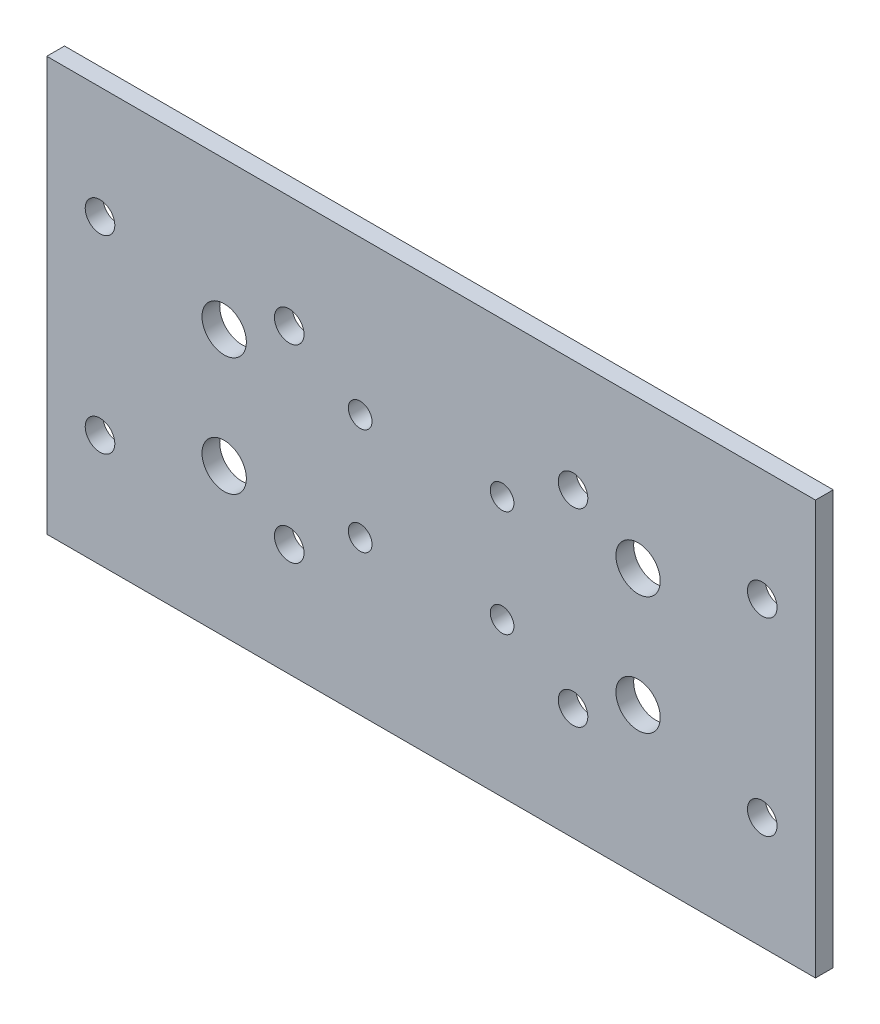
SolidWorks part; units mm, degrees
note: The reader was unsure of these and kept them because the rebuilt part matched: thickness of "Base-Flange1", "Sheet-Metal1", "Sheet-Metal4", "Sheet-Metal5".
material "Wrought Stainless Steel"
ref_plane "Front Plane" through (0, 0, 0) normal (0, 0, 1) x (1, 0, 0)
ref_plane "Top Plane" through (0, 0, 0) normal (0, 1, 0) x (1, 0, 0)
ref_plane "Right Plane" through (0, 0, 0) normal (1, 0, 0) x (0, 0, -1)
sketch "Sketch1" plane through (0, 0, 0) normal (0, 0, 1) x (1, 0, 0)
  line L1 (-65, -35) -> (65, -35)
  line L2 (-65, -35) -> (-65, 35)
  line L3 (-65, 35) -> (65, 35)
  line L4 (65, -35) -> (65, 35)
  line L5 (-65, -35) -> (65, 35) construction
  line L6 (-65, 35) -> (65, -35) construction
  point P0 (0, 0)
  dimension "D1" = 70
  dimension "D2" = 130
base flange "Base-Flange1" sketch "Sketch1" thickness 3 reverse thickness direction yes parameters "D1"=1
sketch "Sketch12" plane through (0, 0, 0) normal (0, 0, -1) x (-1, 0, 0)
  line L0 (0, -1000) -> (0, 49000) construction
  line L1 (-1000, 0) -> (49000, 0) construction
  line L3 (24, -16) -> (56, -16) construction
  line L4 (24, -16) -> (24, 16) construction
  line L5 (24, 16) -> (56, 16) construction
  line L6 (56, -16) -> (56, 16) construction
  line L7 (24, -16) -> (56, 16) construction
  line L8 (24, 16) -> (56, -16) construction
  line L9 (-12, -9) -> (12, -9) construction
  line L10 (-12, -9) -> (-12, 9) construction
  line L11 (-12, 9) -> (12, 9) construction
  line L12 (12, -9) -> (12, 9) construction
  line L13 (-12, -9) -> (12, 9) construction
  line L14 (-12, 9) -> (12, -9) construction
  circle A0 centre (56, 16) radius 2.5
  circle A1 centre (56, -16) radius 2.5
  circle A2 centre (24, -16) radius 2.5
  circle A3 centre (24, 16) radius 2.5
  circle A4 centre (-24, 16) radius 2.5
  circle A5 centre (-24, -16) radius 2.5
  circle A6 centre (-56, -16) radius 2.5
  circle A7 centre (-56, 16) radius 2.5
  circle A8 centre (12, 9) radius 2
  circle A9 centre (-12, 9) radius 2
  circle A10 centre (-12, -9) radius 2
  circle A11 centre (12, -9) radius 2
  point P4 (40, 0)
  point P22 (0, 0)
  dimension "D4" = 5
  dimension "D7" = 4
  dimension "D1" = 32
  dimension "D2" = 32
  dimension "D3" = 56
  dimension "D5" = 24
  dimension "D6" = 18
extrude "Cut-Extrude1" cut sketch "Sketch12" against normal blind 10
sketch "Sketch13" plane through (0, 0, 0) normal (0, 0, -1) x (-1, 0, 0)
  line L1 (-35, -10) -> (35, -10) construction
  line L2 (-35, -10) -> (-35, 10) construction
  line L3 (-35, 10) -> (35, 10) construction
  line L4 (35, -10) -> (35, 10) construction
  line L5 (-35, -10) -> (35, 10) construction
  line L6 (-35, 10) -> (35, -10) construction
  circle A0 centre (35, 10) radius 3.75
  circle A1 centre (-35, 10) radius 3.75
  circle A2 centre (-35, -10) radius 3.75
  circle A3 centre (35, -10) radius 3.75
  point P0 (0, 0)
  dimension "D3" = 7.5
  dimension "D1" = 70
  dimension "D2" = 20
extrude "Cut-Extrude2" cut sketch "Sketch13" against normal blind 10
sketch "Bend-Lines1" [suppressed] plane through (0, 0, 0) normal (0, 1, 0) x (1, 0, 0)
sketch "Bounding-Box1" [suppressed] plane through (0, 0, 0) normal (0, 1, 0) x (1, 0, 0)
sheet metal parameters "Sheet-Metal1" thickness 3 parameters "D1"=1, "D7"=5
flat pattern "Flat-Pattern1" [suppressed]
sketch "Bend-Lines2" plane through (0, 0, 0) normal (0, 1, 0) x (1, 0, 0)
sketch3d "Bounding-Box2" [suppressed]
  line L0 (65, -35, 0) -> (-65, -35, 0) construction
  line L1 (65, 35, 0) -> (-65, 35, 0) construction
  line L2 (65, -35, 0) -> (65, 35, 0) construction
  line L3 (-65, -35, 0) -> (-65, 35, 0) construction
sheet metal parameters "Sheet-Metal4" thickness 3 parameters "D1"=1, "D7"=5
flat pattern "Flat-Pattern1"
sketch "Bend-Lines2" plane through (0, 0, 0) normal (0, 1, 0) x (1, 0, 0)
sketch3d "Bounding-Box2" [suppressed]
  line L0 (65, -35, 0) -> (-65, -35, 0) construction
  line L1 (65, 35, 0) -> (-65, 35, 0) construction
  line L2 (65, -35, 0) -> (65, 35, 0) construction
  line L3 (-65, -35, 0) -> (-65, 35, 0) construction
sheet metal parameters "Sheet-Metal5" thickness 3 parameters "D1"=1, "D7"=5
flat pattern "Flat-Pattern1"
sketch "Bend-Lines2" plane through (0, 0, 0) normal (0, 1, 0) x (1, 0, 0)
sketch3d "Bounding-Box2" [suppressed]
  line L0 (65, -35, 0) -> (-65, -35, 0) construction
  line L1 (65, 35, 0) -> (-65, 35, 0) construction
  line L2 (65, -35, 0) -> (65, 35, 0) construction
  line L3 (-65, -35, 0) -> (-65, 35, 0) construction
